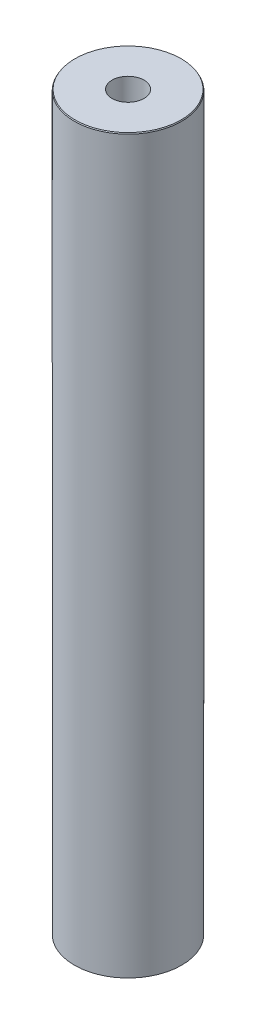
SolidWorks part; units mm, degrees
ref_plane "Front Plane" through (0, 0, 0) normal (0, 0, 1) x (1, 0, 0)
ref_plane "Top Plane" through (0, 0, 0) normal (0, 1, 0) x (1, 0, 0)
ref_plane "Right Plane" through (0, 0, 0) normal (1, 0, 0) x (0, 0, -1)
sketch "Sketch1" plane through (0, 0, 0) normal (0, 1, 0) x (1, 0, 0)
  circle A0 centre (0, 0) radius 35
  dimension "SHAFT_OD" = 70
extrude "Boss-Extrude1" add sketch "Sketch1" along normal blind 478.0201
sketch "Sketch2" plane through (0, 0, 0) normal (0, 1, 0) x (1, 0, 0)
  circle A0 centre (0, 0) radius 10.413
  dimension "BORE_D" = 20.826
extrude "Cut-Extrude1" cut sketch "Sketch2" along normal through all
chamfer "Chamfer1" distance 0.6496 angle 30 2 edges at (0, 478.0201, 35) (0, 0, 35) first distance on face at (0, 478.0201, 35) first distance on face at (0, 0, 10.413)
